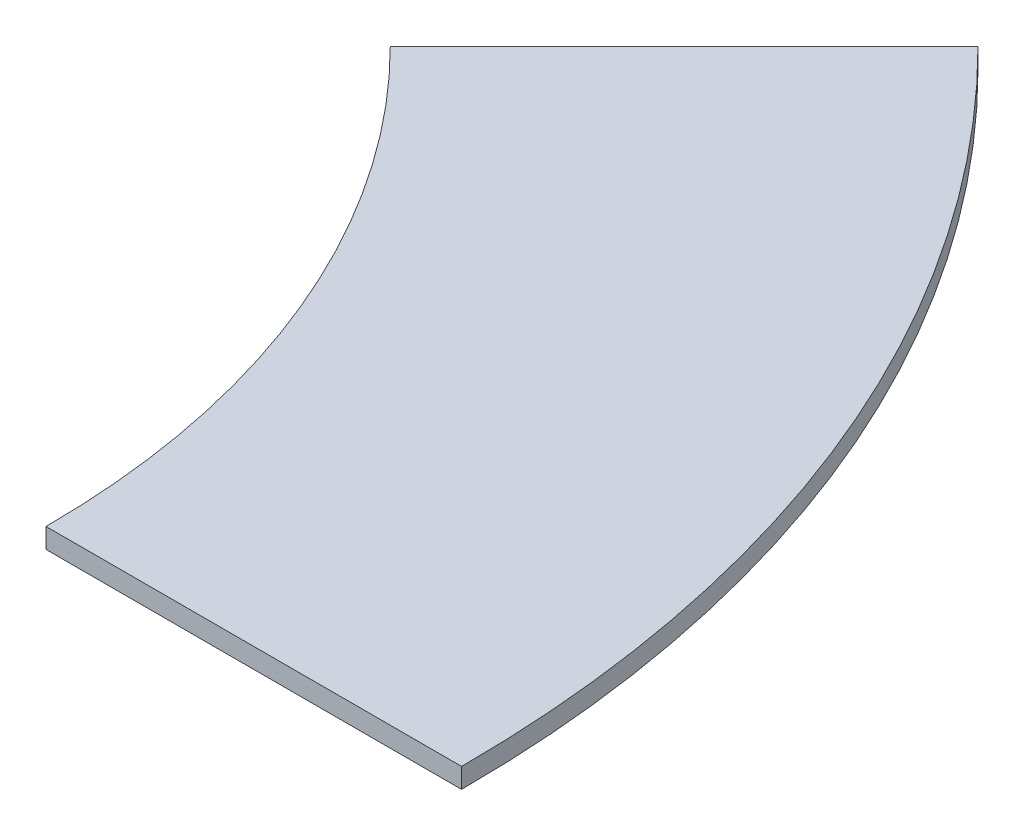
SolidWorks part; units mm, degrees
material "PE High Density"
ref_plane "Front Plane" through (0, 0, 0) normal (0, 0, 1) x (1, 0, 0)
ref_plane "Top Plane" through (0, 0, 0) normal (0, 1, 0) x (1, 0, 0)
ref_plane "Right Plane" through (0, 0, 0) normal (1, 0, 0) x (0, 0, -1)
sketch "Sketch2" plane through (0, 0, 0) normal (0, 0, 1) x (1, 0, 0)
  line L0 (0, 0) -> (0, 22.7316) construction
  line L1 (0, 0) -> (1000, 0)
  line L2 (1000, 12) -> (1000, -12)
  line L3 (1000, 12) -> (1500, 12)
  line L4 (1500, 12) -> (1500, -12)
  line L5 (1500, -12) -> (1000, -12)
  point P7 (1000, 0)
revolve "Revolve1" add sketch "Sketch2" angle 45 about L0
ref_plane "Plane1" through (1060.6602, 12, -1060.6602) normal (0.7071, 0, 0.7071) x (0.7071, 0, -0.7071)
